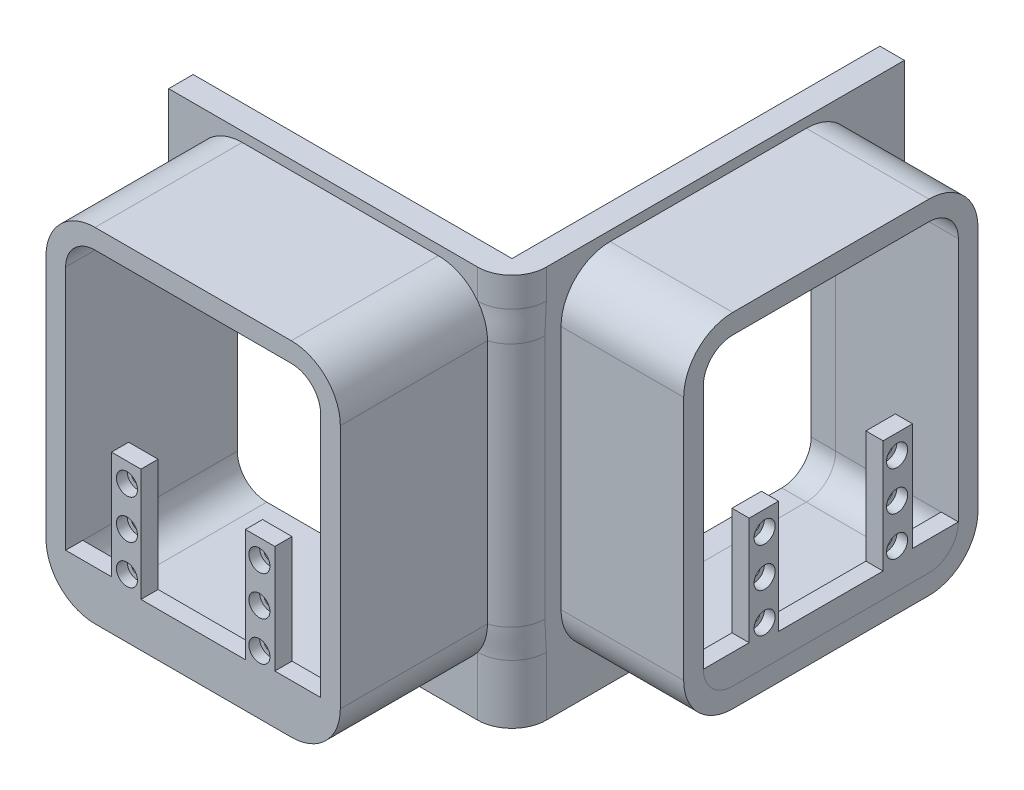
SolidWorks part; units mm, degrees
ref_plane "Front Plane" through (0, 0, 0) normal (0, 0, 1) x (1, 0, 0)
ref_plane "Top Plane" through (0, 0, 0) normal (0, 1, 0) x (1, 0, 0)
ref_plane "Right Plane" through (0, 0, 0) normal (1, 0, 0) x (0, 0, -1)
sketch "Sketch1" plane through (0, 0, 0) normal (0, 0, 1) x (1, 0, 0)
  line L1 (-20, -35) -> (20, -35)
  line L2 (-30, -25) -> (-30, 25)
  line L3 (-20, 35) -> (20, 35)
  line L4 (30, -25) -> (30, 25)
  line L5 (-30, -35) -> (30, 35) construction
  line L6 (-30, 35) -> (30, -35) construction
  arc A1 (20, 35) -> (30, 25) centre (20, 25) cw
  arc A2 (20, -35) -> (30, -25) centre (20, -25) ccw
  arc A3 (-20, -35) -> (-30, -25) centre (-20, -25) cw
  arc A4 (-30, 25) -> (-20, 35) centre (-20, 25) cw
  point P0 (0, 0)
  dimension "D1" = 60
  dimension "D3" = 10
  dimension "D2" = 70
extrude "Boss-Extrude1" add sketch "Sketch1" against normal blind 30
ref_plane "Plane1" through (60, 0, 0) normal (1, 0, 0) x (0, 0, -1)
ref_plane "Plane2" through (60, 0, 0) normal (1, 0, 0) x (0, 0, -1)
sketch "Sketch10" plane through (0, 0, -30) normal (0, 0, -1) x (-1, 0, 0)
  line L0 (0, -3) -> (0, 0) construction
  line L1 (-35, -43) -> (35, -43)
  line L2 (-35, -43) -> (-35, 37)
  line L3 (-35, 37) -> (35, 37)
  line L4 (35, -43) -> (35, 37)
  line L5 (-35, -43) -> (35, 37) construction
  line L6 (-35, 37) -> (35, -43) construction
  point P0 (0, -3)
  dimension "D3" = 3
  dimension "D1" = 80
  dimension "D2" = 70
extrude "Boss-Extrude6" add sketch "Sketch10" along normal blind 80
sketch "Sketch2" plane through (60, 0, 0) normal (1, 0, 0) x (0, 0, -1)
  line L2 (0, 0) -> (146.6861, 0) construction
  line L3 (70, 0) -> (70, 30) construction
  line L5 (30, 37) -> (30, -43) construction
  line L6 (110, 37) -> (110, -43) construction
  line L7 (50, -35) -> (90, -35)
  line L8 (40, -25) -> (40, 25)
  line L9 (50, 35) -> (90, 35)
  line L10 (100, -25) -> (100, 25)
  line L11 (40, -35) -> (100, 35) construction
  line L12 (40, 35) -> (100, -35) construction
  arc A1 (50, -35) -> (40, -25) centre (50, -25) cw
  arc A2 (90, -35) -> (100, -25) centre (90, -25) ccw
  arc A3 (90, 35) -> (100, 25) centre (90, 25) cw
  arc A4 (40, 25) -> (50, 35) centre (50, 25) cw
  dimension "D1" = 60
  dimension "D3" = 10
  dimension "D2" = 70
extrude "Boss-Extrude2" add sketch "Sketch2" against normal up to surface (25 mm away) separate body up to face at (35, -3, -70)
sketch "Sketch11" plane through (0, 37, 0) normal (0, 1, 0) x (1, 0, 0)
  line L1 (-35, 110) -> (30, 110)
  line L2 (-35, 110) -> (-35, 35)
  line L3 (-35, 35) -> (30, 35)
  line L4 (30, 110) -> (30, 35)
  dimension "D1" = 75
  dimension "D2" = 65
extrude "Cut-Extrude5" cut sketch "Sketch11" against normal through all
sketch "Sketch4" plane through (35, 0, 0) normal (-1, 0, 0) x (0, 0, 1)
  line L8 (-90, -31) -> (-50, -31)
  line L9 (-96, 25) -> (-96, -25)
  line L10 (-50, 31) -> (-90, 31)
  line L11 (-44, -25) -> (-44, 25)
  line L12 (-90, -31) -> (-50, -31)
  line L13 (-96, 25) -> (-96, -25)
  line L14 (-50, 31) -> (-90, 31)
  line L15 (-44, -25) -> (-44, 25)
  arc A10 (-96, -25) -> (-90, -31) centre (-90, -25) ccw
  arc A11 (-90, 31) -> (-96, 25) centre (-90, 25) ccw
  arc A12 (-44, 25) -> (-50, 31) centre (-50, 25) ccw
  arc A13 (-50, -31) -> (-44, -25) centre (-50, -25) ccw
  arc A14 (-96, -25) -> (-90, -31) centre (-90, -25) ccw
  arc A15 (-90, 31) -> (-96, 25) centre (-90, 25) ccw
  arc A16 (-44, 25) -> (-50, 31) centre (-50, 25) ccw
  arc A17 (-50, -31) -> (-44, -25) centre (-50, -25) ccw
  dimension "D1" = 4
extrude "Cut-Extrude2" cut sketch "Sketch4" against normal through all contours L12 A17 L15 A16 L14 A15 L13 A14 region at (35, 0, -70)
sketch "Sketch5" plane through (60, 0, 0) normal (1, 0, 0) x (0, 0, -1)
  line L0 (70, 0) -> (70, -31) construction
  line L1 (53.35, -3) -> (59.35, -3)
  line L2 (59.35, -3) -> (59.35, -26)
  line L3 (59.35, -26) -> (80.65, -26)
  line L4 (80.65, -26) -> (80.65, -3)
  line L5 (80.65, -3) -> (86.65, -3)
  line L6 (86.65, -3) -> (86.65, -25)
  line L8 (53.35, -3) -> (53.35, -25)
  line L10 (70, 0) -> (83.5, 0) construction
  line L11 (83.5, 0) -> (83.5, -7) construction
  line L12 (83.5, -7) -> (83.5, -15) construction
  line L13 (83.5, -15) -> (83.5, -23) construction
  line L14 (90, -31) -> (50, -31) construction
  line L15 (50, -31) -> (90, -31)
  line L16 (53.35, -25) -> (44, -25)
  line L17 (86.65, -25) -> (96, -25)
  circle A0 centre (70, 0) radius 11 construction
  arc A1 (44, -25) -> (50, -31) centre (50, -25) ccw construction
  circle A2 centre (83.5, -7) radius 1.25
  arc A3 (44, -25) -> (50, -31) centre (50, -25) ccw
  circle A5 centre (83.5, -15) radius 1.25
  circle A6 centre (83.5, -23) radius 1.25
  circle A7 centre (56.5, -7) radius 1.25
  circle A8 centre (56.5, -15) radius 1.25
  circle A9 centre (56.5, -23) radius 1.25
  arc A10 (90, -31) -> (96, -25) centre (90, -25) ccw
  point P8 (70, -26)
  point P14 (70, -31)
  dimension "D1" = 22
  dimension "D6" = 2.5
  dimension "D3" = 21.3
  dimension "D4" = 13.5
  dimension "D5" = 7
  dimension "D7" = 8
  dimension "D8" = 8
  dimension "D9" = 6
  dimension "D10" = 5
  dimension "D12" = 3
extrude "Boss-Extrude3" add sketch "Sketch5" against normal blind 3.5
sketch "Sketch13" plane through (35, 0, 0) normal (1, 0, 0) x (0, 0, -1)
  line L4 (44, 25) -> (44, -25)
  line L5 (50, -31) -> (90, -31)
  line L6 (96, -25) -> (96, 25)
  line L7 (90, 31) -> (50, 31)
  line L8 (44, 25) -> (44, -25)
  line L9 (50, -31) -> (90, -31)
  line L10 (96, -25) -> (96, 25)
  line L11 (90, 31) -> (50, 31)
  arc A6 (50, 31) -> (44, 25) centre (50, 25) ccw
  arc A7 (44, -25) -> (50, -31) centre (50, -25) ccw
  arc A8 (90, -31) -> (96, -25) centre (90, -25) ccw
  arc A9 (96, 25) -> (90, 31) centre (90, 25) ccw
  arc A10 (50, 31) -> (44, 25) centre (50, 25) ccw
  arc A11 (44, -25) -> (50, -31) centre (50, -25) ccw
  arc A12 (90, -31) -> (96, -25) centre (90, -25) ccw
  arc A13 (96, 25) -> (90, 31) centre (90, 25) ccw
  dimension "D1" = 0
extrude "Cut-Extrude6" cut sketch "Sketch13" against normal up to surface (5 mm away) up to face at (30, -3, -72.5)
sketch "Sketch14" plane through (0, 0, 0) normal (0, 0, 1) x (1, 0, 0)
  line L8 (20, 31) -> (-20, 31)
  line L9 (26, -25) -> (26, 25)
  line L10 (-20, -31) -> (20, -31)
  line L11 (-26, 25) -> (-26, -25)
  line L12 (20, 31) -> (-20, 31)
  line L13 (26, -25) -> (26, 25)
  line L14 (-20, -31) -> (20, -31)
  line L15 (-26, 25) -> (-26, -25)
  arc A10 (26, 25) -> (20, 31) centre (20, 25) ccw
  arc A11 (20, -31) -> (26, -25) centre (20, -25) ccw
  arc A12 (-26, -25) -> (-20, -31) centre (-20, -25) ccw
  arc A13 (-20, 31) -> (-26, 25) centre (-20, 25) ccw
  arc A14 (26, 25) -> (20, 31) centre (20, 25) ccw
  arc A15 (20, -31) -> (26, -25) centre (20, -25) ccw
  arc A16 (-26, -25) -> (-20, -31) centre (-20, -25) ccw
  arc A17 (-20, 31) -> (-26, 25) centre (-20, 25) ccw
  dimension "D1" = 4
extrude "Cut-Extrude7" cut sketch "Sketch14" against normal up to surface (35 mm away) up to face at (-2.5, -3, -35)
sketch "Sketch15" plane through (0, 0, 0) normal (0, 0, 1) x (1, 0, 0)
  line L0 (0, 0) -> (0, -17.9719) construction
  line L1 (-16.65, -3) -> (-10.65, -3)
  line L2 (-10.65, -3) -> (-10.65, -26)
  line L3 (-10.65, -26) -> (10.65, -26)
  line L4 (10.65, -26) -> (10.65, -3)
  line L5 (10.65, -3) -> (16.65, -3)
  line L6 (16.65, -3) -> (16.65, -25)
  line L8 (-16.65, -3) -> (-16.65, -25)
  line L10 (0, 0) -> (13.5, 0) construction
  line L11 (13.5, 0) -> (13.5, -7) construction
  line L12 (13.5, -7) -> (13.5, -15) construction
  line L13 (13.5, -15) -> (13.5, -23) construction
  line L14 (-20, -31) -> (20, -31) construction
  line L15 (-20, -31) -> (20, -31)
  line L16 (26, -25) -> (16.65, -25)
  line L17 (-26, -25) -> (-16.65, -25)
  circle A0 centre (0, 0) radius 11 construction
  circle A1 centre (13.5, -7) radius 1.25
  circle A3 centre (13.5, -15) radius 1.25
  circle A4 centre (13.5, -23) radius 1.25
  circle A5 centre (-13.5, -7) radius 1.25
  circle A6 centre (-13.5, -15) radius 1.25
  circle A7 centre (-13.5, -23) radius 1.25
  arc A9 (-26, -25) -> (-20, -31) centre (-20, -25) ccw
  arc A10 (26, -25) -> (20, -31) centre (20, -25) cw
  point P5 (0, -26)
  dimension "D1" = 22
  dimension "D5" = 2.5
  dimension "D2" = 21.3
  dimension "D3" = 13.5
  dimension "D4" = 7
  dimension "D6" = 8
  dimension "D7" = 8
  dimension "D8" = 6
  dimension "D9" = 5
  dimension "D10" = 3
extrude "Boss-Extrude7" add sketch "Sketch15" against normal blind 3.5
sketch "Sketch16" plane through (60, 0, 0) normal (1, 0, 0) x (0, 0, -1)
  circle A0 centre (83.5, -7) radius 2.15
  circle A1 centre (83.5, -15) radius 2.15
  circle A2 centre (83.5, -23) radius 2.15
  circle A3 centre (56.5, -23) radius 2.15
  circle A4 centre (56.5, -15) radius 2.15
  circle A5 centre (56.5, -7) radius 2.15
  dimension "D1" = 4.3
extrude "Cut-Extrude8" cut sketch "Sketch16" against normal blind 2.2
fillet "Fillet1" radius 7 1 edges at (35, -3, -30)
fillet "Fillet2" radius 10 rebuild error yes
sketch "Sketch17" plane through (0, 0, 0) normal (0, 0, 1) x (1, 0, 0)
  circle A0 centre (-13.5, -7) radius 2.15
  circle A1 centre (-13.5, -15) radius 2.15
  circle A2 centre (-13.5, -23) radius 2.15
  circle A3 centre (13.5, -7) radius 2.15
  circle A4 centre (13.5, -15) radius 2.15
  circle A5 centre (13.5, -23) radius 2.15
  dimension "D1" = 4.3
extrude "Cut-Extrude9" cut sketch "Sketch17" against normal blind 2.2
